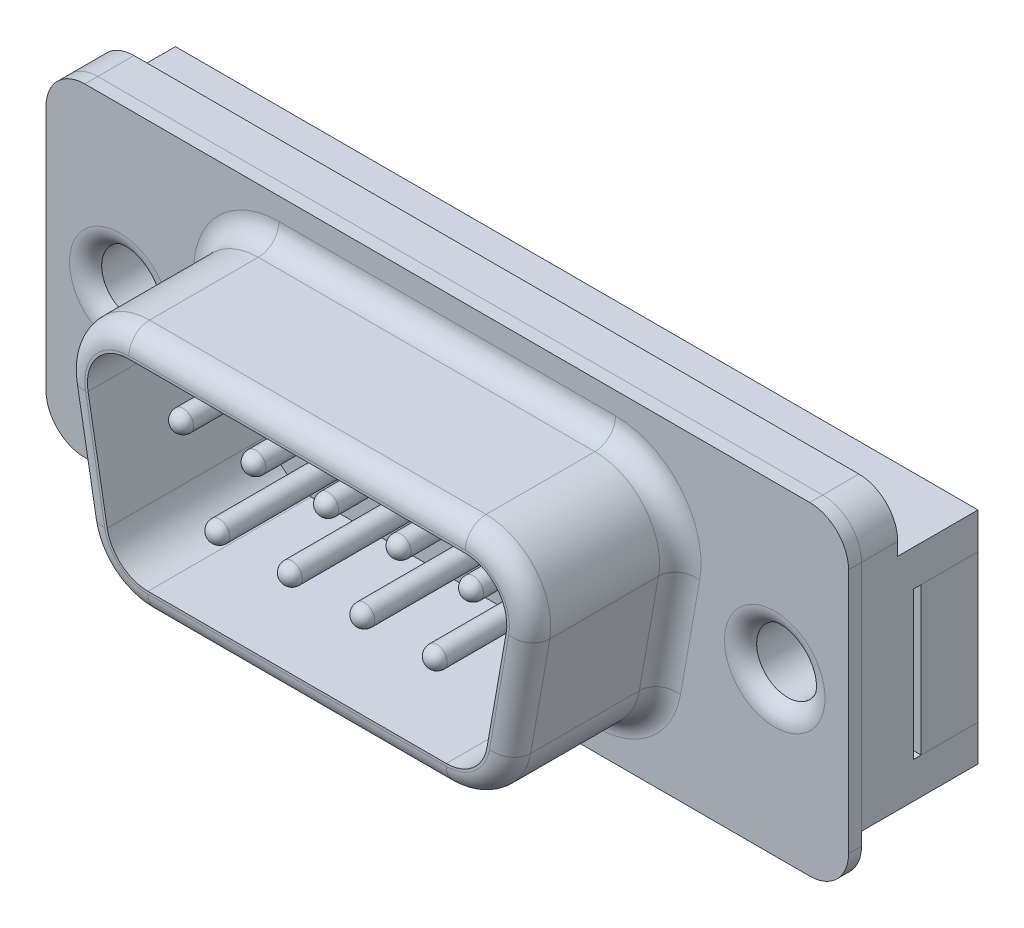
SolidWorks part; units mm, degrees
material "Duranickel(R) 301"
ref_plane "Alzado" through (0, 0, 0) normal (0, 0, 1) x (1, 0, 0)
ref_plane "Planta" through (0, 0, 0) normal (0, 1, 0) x (1, 0, 0)
ref_plane "Vista lateral" through (0, 0, 0) normal (1, 0, 0) x (0, 0, -1)
sketch "Croquis1" plane through (0, 0, 0) normal (0, 0, 1) x (1, 0, 0)
  line L1 (-15.5, 6.25) -> (15.5, 6.25)
  line L2 (-15.5, 6.25) -> (-15.5, -6.25)
  line L3 (-15.5, -6.25) -> (15.5, -6.25)
  line L4 (15.5, 6.25) -> (15.5, -6.25)
  dimension "D1" = 31
  dimension "D2" = 12.5
  dimension "D3" = 15.5
  dimension "D4" = 6.25
extrude "Extruir1" add sketch "Croquis1" along normal blind 0.5
fillet "Redondeo1" radius 1.5 4 edges at (15.5, -6.25, 0.25) (-15.5, -6.25, 0.25) (-15.5, 6.25, 0.25) (15.5, 6.25, 0.25)
sketch "Croquis2" plane through (0, 0, 0.5) normal (0, 0, 1) x (1, 0, 0)
  line L0 (0, -6.25) -> (0, -8.8787) construction
  line L1 (-6.5, 4.6) -> (6.5, 4.6)
  line L2 (-9, 2.1) -> (-9, -4) construction
  line L3 (-5.7594, -4.6) -> (5.7594, -4.6)
  line L4 (9, 4) -> (9, -4) construction
  line L5 (-14, -6.25) -> (14, -6.25) construction
  line L6 (15.5, 0) -> (12.8437, 0) construction
  line L7 (15.5, -4.75) -> (15.5, 4.75) construction
  line L8 (-6.5, 2.1) -> (-5.7594, -2.1) construction
  line L9 (6.5, 2.1) -> (5.7594, -2.1) construction
  line L10 (-8.962, 1.6659) -> (-8.2214, -2.5341)
  line L11 (8.962, 1.6659) -> (8.2214, -2.5341)
  arc A0 (-6.5, 4.6) -> (-8.962, 1.6659) centre (-6.5, 2.1) ccw
  arc A1 (8.962, 1.6659) -> (6.5, 4.6) centre (6.5, 2.1) ccw
  arc A2 (-8.2214, -2.5341) -> (-5.7594, -4.6) centre (-5.7594, -2.1) ccw
  arc A3 (5.7594, -4.6) -> (8.2214, -2.5341) centre (5.7594, -2.1) ccw
  dimension "D5" = 5
  dimension "D6" = 5
  dimension "D7" = 5
  dimension "D8" = 5
  dimension "D9" = 10
  dimension "D2" = 9.2
  dimension "D3" = 9
  dimension "D4" = 4.6
  dimension "D10" = 10
  dimension "D11" = 9
extrude "Extruir2" add sketch "Croquis2" along normal blind 5.8
sketch "Croquis3" plane through (0, 0, 6.3) normal (0, 0, 1) x (1, 0, 0)
  line L0 (-5.7594, -3.7) -> (5.7594, -3.7)
  line L1 (7.3351, -2.3778) -> (8.0757, 1.8222)
  line L2 (6.5, 3.7) -> (-6.5, 3.7)
  line L3 (-8.0757, 1.8222) -> (-7.3351, -2.3778)
  line L4 (-5.7594, -4.6) -> (5.7594, -4.6)
  line L5 (8.2214, -2.5341) -> (8.962, 1.6659)
  line L6 (6.5, 4.6) -> (-6.5, 4.6)
  line L7 (-8.962, 1.6659) -> (-8.2214, -2.5341)
  line L8 (-5.7594, -4.6) -> (5.7594, -4.6) construction
  line L9 (8.2214, -2.5341) -> (8.962, 1.6659) construction
  line L10 (6.5, 4.6) -> (-6.5, 4.6) construction
  line L11 (-8.962, 1.6659) -> (-8.2214, -2.5341) construction
  arc A0 (5.7594, -3.7) -> (7.3351, -2.3778) centre (5.7594, -2.1) ccw
  arc A1 (8.0757, 1.8222) -> (6.5, 3.7) centre (6.5, 2.1) ccw
  arc A2 (-6.5, 3.7) -> (-8.0757, 1.8222) centre (-6.5, 2.1) ccw
  arc A3 (-7.3351, -2.3778) -> (-5.7594, -3.7) centre (-5.7594, -2.1) ccw
  arc A4 (-8.2214, -2.5341) -> (-5.7594, -4.6) centre (-5.7594, -2.1) ccw
  arc A5 (5.7594, -4.6) -> (8.2214, -2.5341) centre (5.7594, -2.1) ccw
  arc A6 (8.962, 1.6659) -> (6.5, 4.6) centre (6.5, 2.1) ccw
  arc A7 (-6.5, 4.6) -> (-8.962, 1.6659) centre (-6.5, 2.1) ccw
  arc A8 (-8.2214, -2.5341) -> (-5.7594, -4.6) centre (-5.7594, -2.1) ccw construction
  arc A9 (5.7594, -4.6) -> (8.2214, -2.5341) centre (5.7594, -2.1) ccw construction
  arc A10 (8.962, 1.6659) -> (6.5, 4.6) centre (6.5, 2.1) ccw construction
  arc A11 (-6.5, 4.6) -> (-8.962, 1.6659) centre (-6.5, 2.1) ccw construction
  dimension "D1" = 0
  dimension "D2" = 0.9
extrude "Cortar-Extruir1" cut sketch "Croquis3" against normal blind 9.8
fillet "Redondeo2" radius 0.8 8 edges at (8.4151, 3.707, 6.3) (8.5917, -0.4341, 6.3) (7.3664, -4.0151, 6.3) (0, -4.6, 6.3) (-7.3664, -4.0151, 6.3) (-8.5917, -0.4341, 6.3) (-8.4151, 3.707, 6.3) (0, 4.6, 6.3)
fillet "Redondeo3" radius 0.8 8 edges at (8.4151, 3.707, 0.5) (8.5917, -0.4341, 0.5) (7.3664, -4.0151, 0.5) (0, -4.6, 0.5) (-7.3664, -4.0151, 0.5) (-8.5917, -0.4341, 0.5) (-8.4151, 3.707, 0.5) (0, 4.6, 0.5)
sketch "Croquis4" plane through (0, 0, 0.5) normal (0, 0, 1) x (1, 0, 0)
  line L0 (14, 6.25) -> (-14, 6.25) construction
  circle A0 centre (12.65, 0) radius 1.2
  circle A1 centre (-12.65, 0) radius 1.2
  point P4 (0, 6.25)
  dimension "D1" = 2.4
  dimension "D2" = 2.4
  dimension "D3" = 25.3
  dimension "D4" = 12.65
  dimension "D5" = 6.25
extrude "Cortar-Extruir2" cut sketch "Croquis4" against normal blind 9.8
fillet "Redondeo4" radius 0.8 2 edges at (-11.45, 0, 0.5) (13.85, 0, 0.5)
sketch "Croquis5" plane through (0, 0, 0) normal (0, 0, -1) x (-1, 0, 0)
  line L0 (-14, 6.25) -> (14, 6.25) construction
  line L1 (-14, 6.25) -> (14, 6.25)
  line L2 (-15.5, -4.25) -> (15.5, -4.25)
  line L3 (15.5, 4.75) -> (15.5, -4.25)
  line L4 (15.5, 4.75) -> (15.5, -4.75) construction
  line L5 (-15.5, 4.75) -> (-15.5, -4.25)
  arc A0 (15.5, 4.75) -> (14, 6.25) centre (14, 4.75) ccw construction
  arc A1 (-14, 6.25) -> (-15.5, 4.75) centre (-14, 4.75) ccw construction
  arc A2 (15.5, 4.75) -> (14, 6.25) centre (14, 4.75) ccw
  arc A3 (-14, 6.25) -> (-15.5, 4.75) centre (-14, 4.75) ccw
  dimension "D1" = 10.5
extrude "Extruir3" add sketch "Croquis5" along normal blind 4.5 separate body
sketch "Croquis6" plane through (15.5, 0, 0) normal (1, 0, 0) x (0, 0, -1)
  line L0 (-0.5, 6.25) -> (-0.5, 4.75) construction
  line L1 (1.4, 7.3662) -> (5.4944, 7.3662)
  line L2 (1.4, 7.3662) -> (1.4, 4.25)
  line L3 (1.4, 4.25) -> (5.4944, 4.25)
  line L4 (5.4944, 7.3662) -> (5.4944, 4.25)
  line L5 (4.5, 6.25) -> (0, 6.25) construction
  dimension "D1" = 1.9
  dimension "D2" = 2
extrude "Cortar-Extruir3" cut sketch "Croquis6" against normal blind 36.5
sketch "Croquis7" plane through (0, 0, -4.5) normal (0, 0, -1) x (-1, 0, 0)
  line L0 (-15.5, 4.25) -> (-15.5, -4.25) construction
  line L1 (-15.5, 2.85) -> (-9.8, 2.85)
  line L2 (-15.5, 2.85) -> (-15.5, -2.85)
  line L3 (-15.5, -2.85) -> (-9.8, -2.85)
  line L4 (-9.8, 2.85) -> (-9.8, -2.85)
  line L5 (0, 6.25) -> (0, 11.7053) construction
  line L6 (-14, 6.25) -> (14, 6.25) construction
  line L7 (9.8, 2.85) -> (9.8, -2.85)
  line L8 (15.5, -2.85) -> (9.8, -2.85)
  line L9 (15.5, 2.85) -> (15.5, -2.85)
  line L10 (15.5, 2.85) -> (9.8, 2.85)
  circle A0 centre (-12.65, 0) radius 1.2 construction
  dimension "D2" = 2.85
  dimension "D1" = 5.7
  dimension "D3" = 5.7
extrude "Cortar-Extruir4" cut sketch "Croquis7" against normal blind 2.5
sketch "Croquis8" plane through (0, 0, -2) normal (0, 0, -1) x (-1, 0, 0)
  circle A0 centre (-12.65, 0) radius 1.2
  circle A1 centre (12.65, 0) radius 1.2
extrude "Cortar-Extruir5" cut sketch "Croquis8" against normal blind 2.5
sketch "Croquis11" plane through (0, 0, -4.5) normal (0, 0, -1) x (-1, 0, 0)
  line L1 (-9.8, 2.85) -> (-15.5, 2.85)
  line L2 (-9.8, 2.85) -> (-9.8, -2.85)
  line L3 (-9.8, -2.85) -> (-15.5, -2.85)
  line L4 (-15.5, 2.85) -> (-15.5, -2.85)
  line L5 (9.8, 2.85) -> (15.5, 2.85)
  line L6 (9.8, 2.85) -> (9.8, -2.85)
  line L7 (9.8, -2.85) -> (15.5, -2.85)
  line L8 (15.5, 2.85) -> (15.5, -2.85)
  circle A0 centre (-12.65, 0) radius 1.2
  circle A1 centre (12.65, 0) radius 1.2
extrude "Extruir5" add sketch "Croquis11" against normal blind 2.2 separate body
sketch "Croquis12" plane through (0, 0, 0) normal (0, 0, 1) x (1, 0, 0)
  line L0 (0, -3.8) -> (0, -8.2949) construction
  line L1 (-5.7594, -3.8) -> (5.7594, -3.8) construction
  circle A0 centre (0, 1.5) radius 0.4
  circle A1 centre (2.8, 1.5) radius 0.4
  circle A2 centre (5.6, 1.5) radius 0.4
  circle A3 centre (-5.6, 1.5) radius 0.4
  circle A4 centre (-2.8, 1.5) radius 0.4
  circle A5 centre (-4.2, -1.5) radius 0.4
  circle A6 centre (-1.4, -1.5) radius 0.4
  circle A7 centre (1.4, -1.5) radius 0.4
  circle A8 centre (4.2, -1.5) radius 0.4
  dimension "D1" = 0.8
  dimension "D2" = 1.5
extrude "Extruir6" add sketch "Croquis12" along normal blind 5.5 separate body
fillet "Redondeo5" radius 0.4 1 edges at (-6, 1.5, 5.5)
fillet "Redondeo6" radius 0.4 1 edges at (-3.2, 1.5, 5.5)
fillet "Redondeo7" radius 0.4 1 edges at (0.4, 1.5, 5.5)
fillet "Redondeo8" radius 0.4 1 edges at (3.2, 1.5, 5.5)
fillet "Redondeo9" radius 0.4 1 edges at (6, 1.5, 5.5)
fillet "Redondeo10" radius 0.4 1 edges at (-4.6, -1.5, 5.5)
fillet "Redondeo11" radius 0.4 1 edges at (-1.8, -1.5, 5.5)
fillet "Redondeo12" radius 0.4 1 edges at (1.8, -1.5, 5.5)
fillet "Redondeo13" radius 0.4 1 edges at (4.6, -1.5, 5.5)
